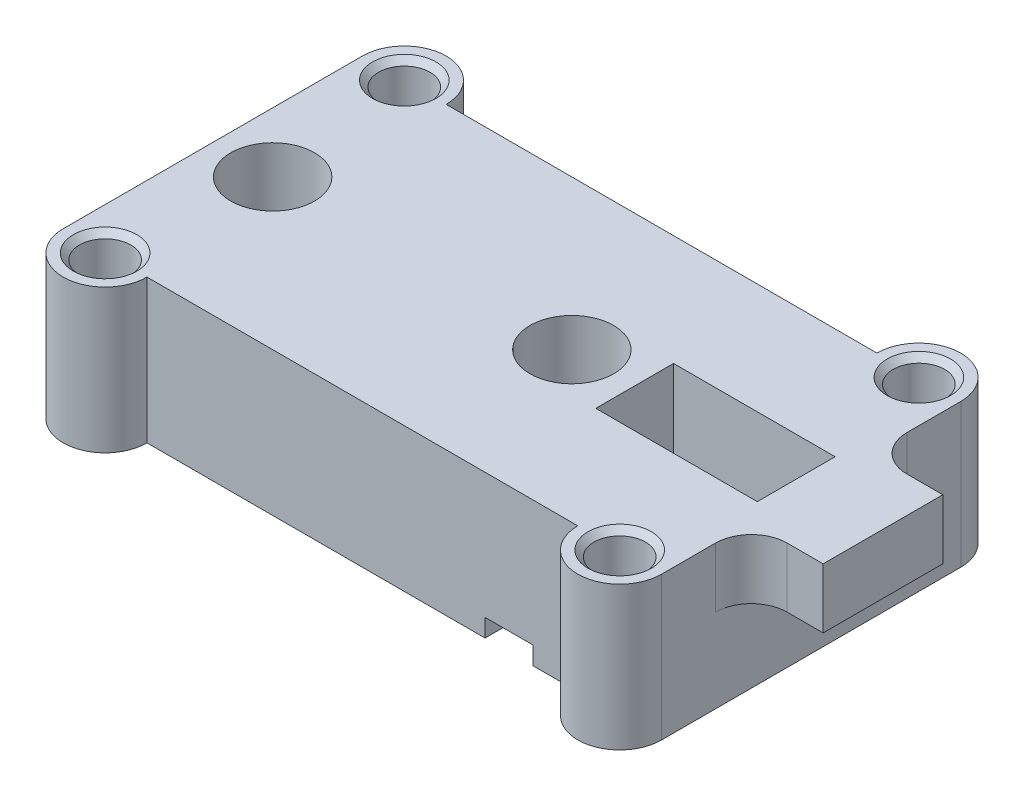
SolidWorks part; units mm, degrees
note: The reader was unsure of these and kept them because the rebuilt part matched: shared geometry of "Sketch2<4>", "Sketch2<6>", "Sketch2<7>", "Sketch2<8>".
material "ABS"
ref_plane "Front Plane" through (0, 0, 0) normal (0, 0, 1) x (1, 0, 0)
ref_plane "Top Plane" through (0, 0, 0) normal (0, 1, 0) x (1, 0, 0)
ref_plane "Right Plane" through (0, 0, 0) normal (1, 0, 0) x (0, 0, -1)
sketch "Sketch2" plane through (0, 0, 0) normal (0, 1, 0) x (1, 0, 0)
  line L0 (-20, 0) -> (0, 0) construction
  line L1 (-25, -12.5) -> (25, -12.5)
  line L2 (-25, -12.5) -> (-25, 12.5)
  line L3 (-25, 12.5) -> (25, 12.5)
  line L4 (25, -12.5) -> (25, 12.5)
  line L5 (-25, -12.5) -> (25, 12.5) construction
  line L6 (-25, 12.5) -> (25, -12.5) construction
  line L7 (-25, 9) -> (25, 9)
  line L8 (-25, -9) -> (25, -9)
  line L9 (0, 0) -> (0, 12.5) construction
  line L10 (0, 0) -> (5, 0) construction
  line L11 (5, 0) -> (17, 0) construction
  line L13 (10.25, -3.25) -> (23.75, -3.25)
  line L14 (10.25, -3.25) -> (10.25, 3.25)
  line L15 (10.25, 3.25) -> (23.75, 3.25)
  line L16 (23.75, -3.25) -> (23.75, 3.25)
  line L17 (10.25, -3.25) -> (23.75, 3.25) construction
  line L18 (10.25, 3.25) -> (23.75, -3.25) construction
  line L19 (17, 0) -> (28, 0) construction
  line L20 (10.25, -1.75) -> (23.75, -1.75)
  line L21 (10.25, -1.75) -> (10.25, 1.75)
  line L22 (10.25, 1.75) -> (23.75, 1.75)
  line L23 (23.75, -1.75) -> (23.75, 1.75)
  line L24 (10.25, -1.75) -> (23.75, 1.75) construction
  line L25 (10.25, 1.75) -> (23.75, -1.75) construction
  line L27 (31, 5) -> (25, 5)
  line L28 (31, 5) -> (31, -5)
  line L29 (31, -5) -> (25, -5)
  line L30 (25, 5) -> (25, -5)
  line L31 (31, 5) -> (25, -5) construction
  line L32 (31, -5) -> (25, 5) construction
  circle A0 centre (-20, 0) radius 1.75
  circle A1 centre (5, 0) radius 1.75
  circle A2 centre (-21.5, 12.5) radius 2.15
  circle A3 centre (-21.5, 12.5) radius 3.5
  circle A4 centre (21.5, 12.5) radius 3.5
  circle A5 centre (21.5, 12.5) radius 2.15
  circle A6 centre (21.5, -12.5) radius 3.5
  circle A7 centre (21.5, -12.5) radius 2.15
  circle A8 centre (-21.5, -12.5) radius 3.5
  circle A9 centre (-21.5, -12.5) radius 2.15
  circle A10 centre (-20, 0) radius 3.5
  circle A11 centre (5, 0) radius 3.5
  point P0 (0, 0)
  point P9 (0, 0)
  point P37 (23.75, 1.75)
  point P46 (0, 0)
  point P47 (0, 0)
  point P48 (0, 0)
  point P49 (16.9523, 0)
  point P50 (23.75, 1.75)
  dimension "D1" = 3.5
  dimension "D7" = 4.3
  dimension "D13" = 7
  dimension "D2" = 6.5
  dimension "D3" = 50
  dimension "D4" = 25
  dimension "D8" = 20
  dimension "D9" = 13.5
  dimension "D10" = 12
  dimension "D11" = 5
  dimension "D12" = 3.5
  dimension "D14" = 6
  dimension "D15" = 10
  dimension "D5" = 3.5
  dimension "D6" = 3.5
extrude "Boss-Extrude2" add sketch "Sketch2" along normal blind 12 contours L22 L16 L20 L4 | L20 L14 L13 L16 | L14 L22 L16 L15 | L16 L22 L4 L7 L2 L8 L20 L13 L14 L15 A1 A0 | L8 A8 L1 A6 | L2 A8 L8 | L1 A9 A8 | A9 L1 | L1 A9 A8 | A9 L1 | A7 L1 A6 | L1 A7 | L1 A7 | A7 L1 A6 | A6 L4 L8 | L3 A5 A4 | L3 A5 A4 | A5 L3 | A5 L3 | L7 A4 L3 A3 | L4 A4 L7 | A3 L3 A2 | A3 L2 L7 | L3 A3 A2 | L3 A2 | L3 A2 | A10 A0 | A11 A1
extrude "Boss-Extrude3" add sketch "Sketch2<4>" against normal blind 5 from surface at 12 contours L29 L28 L27 L4 starting at face at (0, 12, 0)
sketch "Sketch2<4>" plane through (0, 0, 0) normal (0, 1, 0) x (1, 0, 0) same geometry as "Sketch2"
extrude "Cut-Extrude1" cut sketch "Sketch2<6>" against normal blind 9.3 from surface at 12 contours L20 L14 L13 L16 | L14 L22 L16 L15 starting at face at (9.3333, 12, 0)
sketch "Sketch2<6>" plane through (0, 0, 0) normal (0, 1, 0) x (1, 0, 0) same geometry as "Sketch2"
extrude "Cut-Extrude2" cut sketch "Sketch2<7>" against normal blind 4.5 from surface at 12 contours A5 L3 | A5 L3 | L1 A7 | L1 A7 | L3 A2 | L3 A2 | A9 L1 | A9 L1 starting at face at (9.3333, 12, 0)
sketch "Sketch2<7>" plane through (0, 0, 0) normal (0, 1, 0) x (1, 0, 0) same geometry as "Sketch2"
extrude "Cut-Extrude3" cut sketch "Sketch2<8>" against normal offset from surface (8.5 mm away) 3.5 from surface at 12 contours A10 A0 | A11 A1 up to face at (0, 0, 0) starting at face at (21.5, 12, 14.65)
sketch "Sketch2<8>" plane through (0, 0, 0) normal (0, 1, 0) x (1, 0, 0) same geometry as "Sketch2"
fillet "Fillet1" radius 3 2 edges at (25, 9.5, -5) (25, 9.5, 5)
chamfer "Chamfer1" distance 0.5 angle 45 4 edges at (21.5, 12, -10.35) (-21.5, 12, -10.35) (-21.5, 12, 14.65) (21.5, 12, 14.65)
sketch "Sketch3" plane through (0, 0, 0) normal (0, -1, 0) x (1, 0, 0)
  line L0 (10.25, 1.75) -> (10.25, 12.5)
  line L1 (-18, 12.5) -> (18, 12.5) construction
  line L2 (10.25, 12.5) -> (14.25, 12.5)
  line L3 (14.25, 12.5) -> (23.75, 1.75)
  line L4 (23.75, 1.75) -> (10.25, 1.75)
  dimension "D1" = 4
extrude "Cut-Extrude4" cut sketch "Sketch3" against normal blind 1.5
